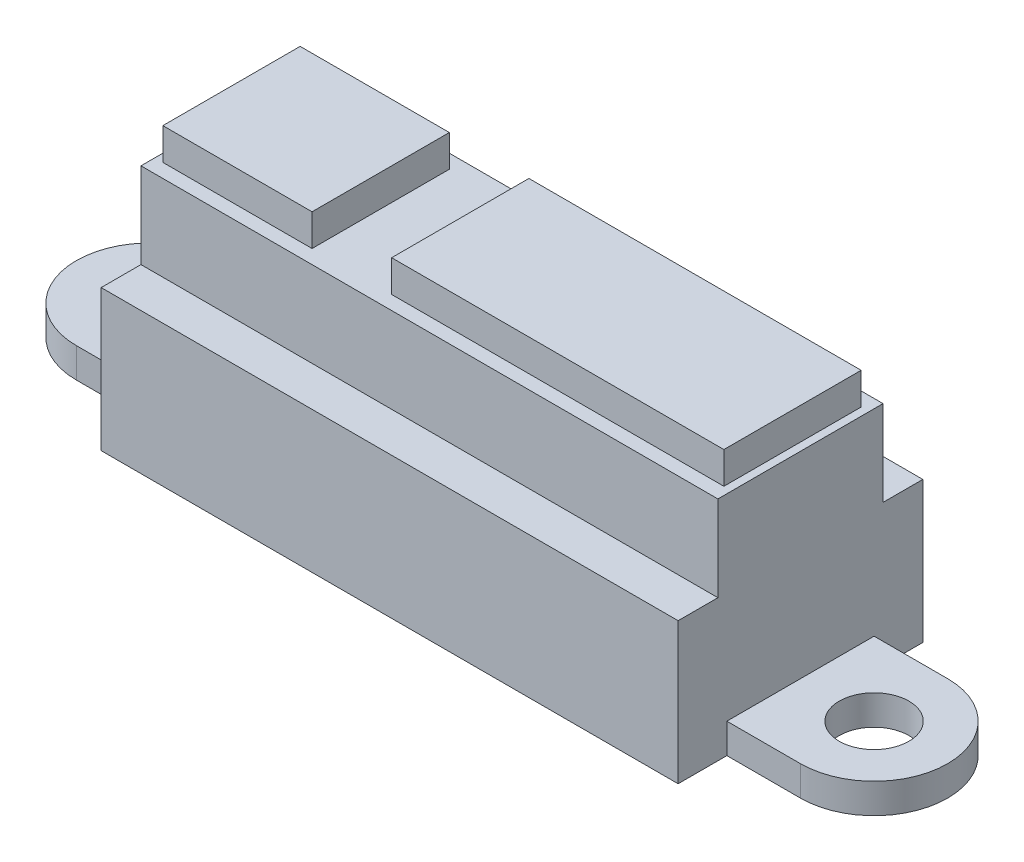
SolidWorks part; units mm, degrees
ref_plane "Plano frontal" through (0, 0, 0) normal (0, 0, 1) x (1, 0, 0)
ref_plane "Plano superior" through (0, 0, 0) normal (0, 1, 0) x (1, 0, 0)
ref_plane "Plano direito" through (0, 0, 0) normal (1, 0, 0) x (0, 0, -1)
sketch "Esboço1" plane through (0, 0, 0) normal (0, 0, 1) x (1, 0, 0)
  line L0 (-14.1, 13) -> (-14.1, 11.4)
  line L1 (-14.1, 13) -> (-6.6, 13)
  line L2 (-14.5, 11.4) -> (-14.5, 1.5)
  line L3 (-14.5, 0) -> (14.5, 0)
  line L4 (-14.5, 1.5) -> (-21.9, 1.5)
  line L5 (-21.9, 1.5) -> (-21.9, 0)
  line L6 (-21.9, 0) -> (-14.5, 0)
  line L7 (-14.1, 11.4) -> (-14.5, 11.4)
  line L8 (14.1, 11.4) -> (14.5, 11.4)
  line L9 (21.9, 0) -> (14.5, 0)
  line L10 (0, 16.8208) -> (0, 0) construction
  line L11 (21.9, 1.5) -> (21.9, 0)
  line L12 (14.5, 1.5) -> (21.9, 1.5)
  line L13 (14.5, 11.4) -> (14.5, 1.5)
  line L14 (14.1, 13) -> (14.1, 11.4)
  line L15 (-6.6, 13) -> (-6.6, 11.4)
  line L16 (-6.6, 11.4) -> (-2.6, 11.4)
  line L17 (-2.6, 11.4) -> (-2.6, 13)
  line L18 (-2.6, 13) -> (14.1, 13)
  point P0 (0, 0)
  point P18 (0, 0)
  point P23 (0, 16.8208)
  dimension "D1" = 29
  dimension "D2" = 13
  dimension "D3" = 1.6
  dimension "D4" = 0.4
  dimension "D5" = 7.4
  dimension "D6" = 1.5
  dimension "D7" = 7.5
  dimension "D8" = 4
extrude "Ressalto-extrusão1" add sketch "Esboço1" along normal blind 12.3
sketch "Esboço2" plane through (0, 13, 0) normal (0, 1, 0) x (1, 0, 0)
  line L0 (-21.9, -6.15) -> (21.9, -6.15) construction
  line L1 (-21.9, -12.3) -> (-21.9, 0) construction
  line L2 (21.9, -12.3) -> (21.9, 0) construction
  line L3 (-18.2, -2.45) -> (-14.5, -2.45)
  line L4 (-14.5, -12.3) -> (-14.5, 0) construction
  line L5 (-14.5, -2.45) -> (-14.5, 0)
  line L6 (-18.2, -9.85) -> (-14.5, -9.85)
  line L7 (-14.5, -9.85) -> (-14.5, -12.3)
  line L8 (-14.5, 0) -> (-21.9, 0)
  line L9 (-21.9, -12.3) -> (-21.9, 0)
  line L10 (-21.9, -12.3) -> (-14.5, -12.3)
  line L11 (0, 0) -> (0, -12.9333) construction
  line L12 (21.9, -12.3) -> (14.5, -12.3)
  line L13 (21.9, -12.3) -> (21.9, 0)
  line L14 (14.5, 0) -> (21.9, 0)
  line L15 (14.5, -9.85) -> (14.5, -12.3)
  line L16 (18.2, -9.85) -> (14.5, -9.85)
  line L17 (14.5, -2.45) -> (14.5, 0)
  line L18 (18.2, -2.45) -> (14.5, -2.45)
  arc A0 (-18.2, -2.45) -> (-18.2, -9.85) centre (-18.2, -6.15) ccw
  arc A1 (18.2, -2.45) -> (18.2, -9.85) centre (18.2, -6.15) cw
  circle A2 centre (-18.2, -6.15) radius 1.75
  circle A3 centre (18.2, -6.15) radius 1.75
  dimension "D1" = 7.4
  dimension "D2" = 3.5
extrude "Corte-extrusão1" cut sketch "Esboço2" against normal blind 22.3 contours A0 L9 L10 L7 L6 | A0 L3 L5 L8 L9 | L18 A1 L13 L14 L17 | L13 A1 L16 L15 L12 | A2 | A3 region at (-18.6007, 13, 1.5111) region at (-18.6007, 13, 10.7889) region at (18.6007, 13, 1.5111) region at (18.6007, 13, 10.7889) region at (-18.2, 13, 6.15) region at (18.2, 13, 6.15)
sketch "Esboço3" plane through (-14.5, 0, 0) normal (-1, 0, 0) x (0, 0, 1)
  line L0 (2.7, 13) -> (2.7, 11.4)
  line L1 (12.3, 13) -> (0, 13) construction
  line L2 (12.3, 11.4) -> (0, 11.4) construction
  line L3 (2.7, 11.4) -> (2, 11.4)
  line L4 (12.3, 11.4) -> (0, 11.4) construction
  line L5 (2, 11.4) -> (2, 7.1)
  line L6 (2, 7.1) -> (0, 7.1)
  line L7 (0, 11.4) -> (0, 0) construction
  line L8 (6.15, 13) -> (6.15, 6.194) construction
  line L9 (2.7, 13) -> (0, 13)
  line L10 (0, 13) -> (0, 7.1)
  line L11 (12.3, 13) -> (12.3, 7.1)
  line L12 (9.6, 13) -> (12.3, 13)
  line L13 (10.3, 7.1) -> (12.3, 7.1)
  line L14 (10.3, 11.4) -> (10.3, 7.1)
  line L15 (9.6, 11.4) -> (10.3, 11.4)
  line L16 (9.6, 13) -> (9.6, 11.4)
  dimension "D1" = 4.3
  dimension "D2" = 2
  dimension "D3" = 0.7
extrude "Corte-extrusão2" cut sketch "Esboço3" against normal blind 32.3
